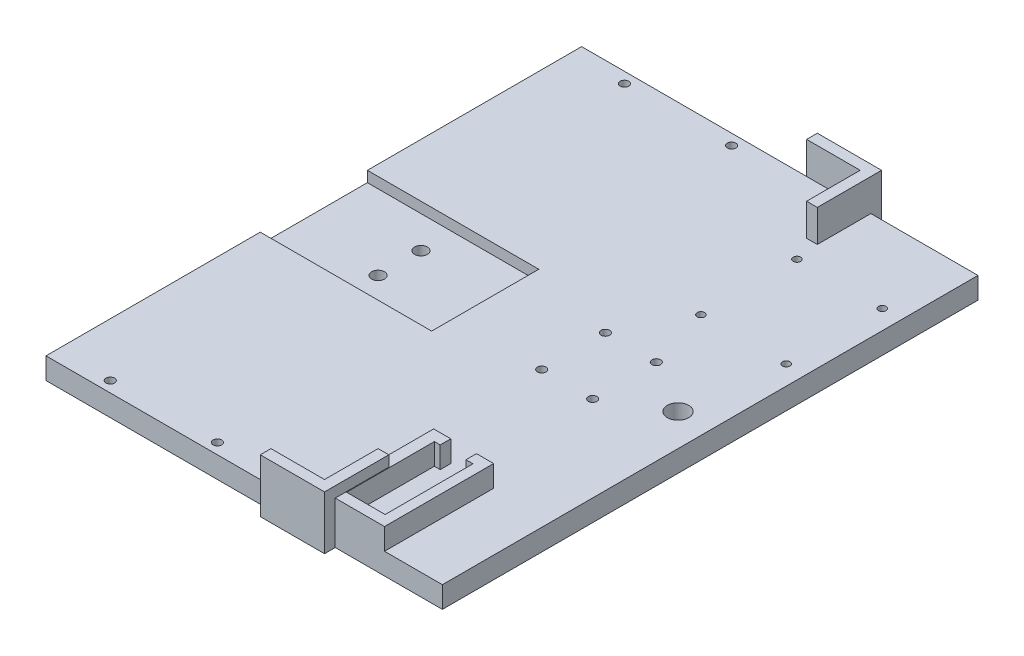
SolidWorks part; units mm, degrees
ref_plane "Ebene vorne" through (0, 0, 0) normal (0, 0, 1) x (1, 0, 0)
ref_plane "Ebene oben" through (0, 0, 0) normal (0, 1, 0) x (1, 0, 0)
ref_plane "Ebene rechts" through (0, 0, 0) normal (1, 0, 0) x (0, 0, -1)
sketch "Skizze1" plane through (0, 0, 0) normal (0, 1, 0) x (1, 0, 0)
  line L5 (-175, -125) -> (175, 125) construction
  line L6 (-175, 125) -> (175, -125) construction
  line L11 (-105, 125) -> (145, 125)
  line L12 (-105, -125) -> (-105, -65)
  line L13 (-105, 125) -> (-105, 65)
  line L14 (-105, -65) -> (-175, -65)
  line L15 (-105, 65) -> (-175, 65)
  line L17 (-105, -125) -> (145, -125)
  line L19 (185, 20) -> (145, 125)
  line L21 (175, 0) -> (175, 20)
  line L22 (175, 20) -> (185, 20)
  line L23 (185, 0) -> (185, 20)
  line L25 (185, 0) -> (185, -20)
  line L26 (185, -20) -> (175, -20)
  line L27 (175, 0) -> (175, -20)
  line L28 (185, -20) -> (145, -125)
  line L29 (-175, 65) -> (-175, -65)
  point P0 (0, 0)
  dimension "D1" = 350
  dimension "D2" = 250
  dimension "D3" = 60
  dimension "D4" = 250
  dimension "D5" = 40
  dimension "D6" = 130
  dimension "D7" = 70
  dimension "D8" = 20
  dimension "D9" = 10
extrude "Aufsatz-Linear austragen1" add sketch "Skizze1" along normal blind 15 contours L15 L29 L14 L12 L17 L28 L26 L27 L21 L22 L19 L11 L13 | L21 L27 L26 L25 L23 L22 region at (10.8182, 0, 0) region at (180, 0, 0)
sketch "Skizze2" plane through (0, 15, 0) normal (0, 1, 0) x (1, 0, 0)
  line L0 (-175, 65) -> (-175, -65) construction
  line L9 (-175, 62) -> (-110, 62)
  line L10 (-175, 62) -> (-175, 42)
  line L11 (-175, 42) -> (-110, 42)
  line L12 (-110, 62) -> (-110, 42)
  line L13 (-105, 65) -> (-175, 65) construction
  line L14 (-175, -42) -> (-110, -42)
  line L15 (-175, -42) -> (-175, -62)
  line L16 (-175, -62) -> (-110, -62)
  line L17 (-110, -42) -> (-110, -62)
  line L18 (-105, -65) -> (-175, -65) construction
  line L19 (-105, 125) -> (145, 125) construction
  line L24 (-125, -62) -> (-120, -62)
  line L25 (-125, -62) -> (-125, -65)
  line L26 (-125, -65) -> (-120, -65)
  line L27 (-120, -62) -> (-120, -65)
  line L28 (-125, -42) -> (-120, -42)
  line L29 (-125, -42) -> (-125, -38)
  line L30 (-125, -38) -> (-120, -38)
  line L31 (-120, -42) -> (-120, -38)
  line L32 (-125, 42) -> (-120, 42)
  line L33 (-125, 42) -> (-125, 38)
  line L34 (-125, 38) -> (-120, 38)
  line L35 (-120, 42) -> (-120, 38)
  line L36 (-125, 65) -> (-120, 65)
  line L37 (-125, 65) -> (-125, 62)
  line L38 (-125, 62) -> (-120, 62)
  line L39 (-120, 65) -> (-120, 62)
  line L40 (-105, -125) -> (145, -125)
  line L41 (-105, -125) -> (-105, 125)
  line L42 (-105, 125) -> (145, 125)
  line L43 (145, -125) -> (145, 125)
  line L46 (145, -125) -> (195, -125)
  line L47 (145, -125) -> (145, 125)
  line L48 (145, 125) -> (195, 125)
  line L49 (195, -125) -> (195, 125)
  line M8 (-105, 65) -> (-175, 65)
  dimension "D1" = 65
  dimension "D2" = 65
  dimension "D3" = 20
  dimension "D4" = 20
  dimension "D5" = 3
  dimension "D6" = 3
  dimension "D7" = 5
  dimension "D8" = 50
  dimension "D9" = 5
  dimension "D10" = 50
  dimension "D11" = 5
  dimension "D12" = 50
  dimension "D13" = 5
  dimension "D14" = 50
  dimension "D15" = 4
  dimension "D16" = 4
  dimension "D17" = 250
  dimension "D18" = 50
extrude "Aufsatz-Linear austragen2" add sketch "Skizze2" against normal blind 37 contours L14 L31 L30 L29 | L35 L11 L33 L34 | L39 L37 L9 M8 | L26 L27 L24 L25 region at (-122.5, 15, -63.5) region at (-122.5, 15, -40) region at (-122.5, 15, 40)
sketch "Skizze3" plane through (0, 15, 0) normal (0, 1, 0) x (1, 0, 0)
  line L0 (-105, 125) -> (145, 125) construction
  line L1 (-105, -125) -> (145, -125)
  line L2 (-105, -125) -> (-105, 125)
  line L3 (-105, 125) -> (145, 125)
  line L4 (145, -125) -> (145, 125)
  line L6 (145, -125) -> (195, -125)
  line L7 (145, -125) -> (145, 125)
  line L8 (145, 125) -> (195, 125)
  line L9 (195, -125) -> (195, 125)
  line M6 (145, -125) -> (185, -20)
  line M7 (185, -20) -> (185, 20)
  line M8 (185, 20) -> (145, 125)
  dimension "D1" = 250
  dimension "D2" = 50
extrude "Aufsatz-Linear austragen3" add sketch "Skizze3" against normal blind 15 contours L6 L9 L8 M8 M7 M6 region at (167.3825, 15, 73.4076)
sketch "Skizze4" plane through (0, 15, 0) normal (0, 1, 0) x (1, 0, 0)
  line L9 (195, -125) -> (200, -125)
  line L10 (195, -125) -> (195, 125)
  line L11 (195, 125) -> (200, 125)
  line L12 (200, -125) -> (200, 125)
  dimension "D3" = 250
  dimension "D4" = 5
extrude "Aufsatz-Linear austragen4" add sketch "Skizze4" against normal blind 15
sketch "Skizze5" plane through (0, 15, 0) normal (0, 1, 0) x (1, 0, 0)
  line L1 (-105, 125) -> (-75, 125)
  line L2 (-105, 125) -> (-105, 120)
  line L3 (-105, 120) -> (-75, 120)
  line L4 (-75, 125) -> (-75, 120)
  line L5 (-105, -125) -> (-75, -125)
  line L6 (-105, -125) -> (-105, -120)
  line L7 (-105, -120) -> (-75, -120)
  line L8 (-75, -125) -> (-75, -120)
  dimension "D1" = 30
  dimension "D2" = 30
  dimension "D3" = 5
  dimension "D4" = 5
extrude "Aufsatz-Linear austragen5" add sketch "Skizze5" against normal blind 30
sketch "Skizze6" plane through (0, 15, 0) normal (0, 1, 0) x (1, 0, 0)
  line L0 (-105, -125) -> (200, -125) construction
  line L1 (-110, -130) -> (-70.4119, -130)
  line L2 (-110, -130) -> (-110, -86.8064)
  line L3 (-110, -86.8064) -> (-70.4119, -86.8064)
  line L4 (-70.4119, -130) -> (-70.4119, -86.8064)
  line L5 (-110, 130) -> (-61.5934, 130)
  line L6 (-110, 130) -> (-110, 88.8696)
  line L7 (-110, 88.8696) -> (-61.5934, 88.8696)
  line L8 (-61.5934, 130) -> (-61.5934, 88.8696)
  line L9 (-105, -125) -> (-105, -65) construction
  line L10 (-105, 125) -> (-105, 65) construction
  line L11 (-105, 125) -> (200, 125) construction
  line L12 (-68.8744, -125) -> (-105, -125)
  line L13 (-105, -125) -> (-105, -86.8064)
  line L14 (-105, 84.0053) -> (-105, 125)
  line L15 (-105, 125) -> (-61.5934, 125)
  line M6 (-105, -65) -> (-105, -125)
  line M7 (-105, -125) -> (200, -125)
  line M9 (200, 125) -> (-105, 125)
  line M10 (-105, 125) -> (-105, 65)
  dimension "D1" = 5
  dimension "D2" = 5
  dimension "D3" = 5
  dimension "D4" = 5
extrude "Aufsatz-Linear austragen6" add sketch "Skizze6" along normal blind 15 separate body contours L8 L5 L6 L7 M10 M9 | L1 L4 L3 L2 M7 M6 region at (-109.4141, 15, 108.4032) region at (-85.7967, 15, -129.3648)
sketch "Skizze7" plane through (0, 0, 0) normal (0, -1, 0) x (1, 0, 0)
  line L7 (-110, -130) -> (-110, -88.8696)
  line L8 (-110, -88.8696) -> (-105, -88.8696)
  line L9 (-105, -130) -> (-105, -88.8696)
  line L10 (-110, 130) -> (-105, 130)
  line L11 (-110, 130) -> (-110, 86.8064)
  line L12 (-110, 86.8064) -> (-105, 86.8064)
  line L13 (-105, 130) -> (-105, 86.8064)
  line L14 (-110, 130) -> (-70.4119, 130)
  line L15 (-110, 130) -> (-110, 125)
  line L16 (-110, 125) -> (-70.4119, 125)
  line L17 (-70.4119, 130) -> (-70.4119, 125)
  line L18 (-110, -130) -> (-61.5934, -130)
  line L19 (-110, -130) -> (-110, -125)
  line L20 (-110, -125) -> (-61.5934, -125)
  line L21 (-61.5934, -130) -> (-61.5934, -125)
  line M7 (-105, 120) -> (-105, 65)
  line M19 (-105, -65) -> (-105, -120)
  line M22 (-75, -125) -> (200, -125)
  line M24 (200, 125) -> (-75, 125)
extrude "Aufsatz-Linear austragen7" add sketch "Skizze7" against normal blind 15 contours L7 L20 L9 L8 M19 | L20 L7 L18 L9 | L18 L21 L20 L9 M22 | L16 L11 L12 L13 M7 | L11 L16 L13 L10 | L17 L14 L13 L16 M24 region at (-107.5, 0, -127.5) region at (-107.5, 0, -106.9348) region at (-83.2967, 0, -127.5) region at (-107.5, 0, 127.5) region at (-87.7059, 0, 127.5) region at (-107.5, 0, 105.9032)
sketch "Skizze8" plane through (0, 15, 0) normal (0, 1, 0) x (1, 0, 0)
  line L0 (-61.5934, 125) -> (200, 125) construction
  line L1 (-105, -125) -> (145, -125)
  line L2 (-105, -125) -> (-105, 125)
  line L3 (-105, 125) -> (145, 125)
  line L4 (145, -125) -> (145, 125)
  line L6 (150, -130) -> (109.2888, -130)
  line L7 (150, -130) -> (150, -94.2536)
  line L8 (150, -94.2536) -> (109.2888, -94.2536)
  line L9 (109.2888, -130) -> (109.2888, -94.2536)
  line L10 (150, 130) -> (118.9946, 130)
  line L11 (150, 130) -> (150, 95.9912)
  line L12 (150, 95.9912) -> (118.9946, 95.9912)
  line L13 (118.9946, 130) -> (118.9946, 95.9912)
  line M9 (-70.4119, -125) -> (200, -125)
  line M11 (200, 125) -> (-61.5934, 125)
  dimension "D1" = 250
  dimension "D2" = 5
  dimension "D3" = 5
  dimension "D4" = 5
  dimension "D5" = 5
extrude "Aufsatz-Linear austragen8" add sketch "Skizze8" along normal blind 15 and the other way blind 15 contours L7 L8 L4 M9 | L9 L6 L7 L1 M9 | L12 L11 L4 M11 | L10 L13 L11 M11 region at (129.6444, 15, 127.5) region at (147.5, 15, 109.6268) region at (134.4973, 15, -127.5) region at (147.5, 15, -110.4956)
sketch "Skizze9" plane through (0, 15, 0) normal (0, 1, 0) x (1, 0, 0)
  line L1 (150, -125) -> (200, -125)
  line L2 (150, -125) -> (150, 125)
  line L3 (150, 125) -> (200, 125)
  line L4 (200, -125) -> (200, 125)
  line L5 (150, 9) -> (196, 9)
  line L6 (150, 9) -> (150, 120)
  line L7 (150, 120) -> (196, 120)
  line L8 (196, 9) -> (196, 120)
  line L10 (200, 105) -> (196, 105)
  line L12 (155, 4) -> (145, 4)
  line L13 (155, 4) -> (155, 14)
  line L14 (155, 14) -> (145, 14)
  line L15 (145, 4) -> (145, 14)
  line L17 (190, 14) -> (200, 14)
  line L18 (190, 14) -> (190, 4)
  line L19 (190, 4) -> (200, 4)
  line L20 (200, 14) -> (200, 4)
  line M10 (150, 125) -> (150, 95.9912)
  line M31 (200, 125) -> (150, 125)
  dimension "D1" = 46
  dimension "D2" = 111
  dimension "D3" = 5
  dimension "D4" = 20
  dimension "D5" = 10
  dimension "D6" = 10
  dimension "D7" = 5
  dimension "D8" = 5
  dimension "D9" = 10
  dimension "D10" = 10
  dimension "D11" = 5
extrude "Aufsatz-Linear austragen10" add sketch "Skizze9" along normal blind 15 contours L15 L12 L2 L14 | L12 L13 L5 L2 | L18 L19 L4 L17 L8 L5 | L10 L4 L7 L8 M31 M10 region at (147.5, 15, -9) region at (152.5, 15, -6.5) region at (195.8571, 15, -7.9286) region at (179.4516, 15, -120.5645)
sketch "Skizze10" plane through (118.9946, 0, 0) normal (-1, 0, 0) x (0, 0, 1)
  line L1 (-125, 30) -> (-130, 30)
  line L2 (-125, 30) -> (-125, 0)
  line L3 (-125, 0) -> (-130, 0)
  line L4 (-130, 30) -> (-130, 0)
extrude "Schnitt-Linear austragen1" cut sketch "Skizze10" against normal blind 1.01
sketch "Skizze12" plane through (0, 15, 0) normal (0, 1, 0) x (1, 0, 0)
  line L0 (-105, 125) -> (-105, 88.8696) construction
  line L1 (-110, 130) -> (-105, 130)
  line L2 (-110, 130) -> (-110, 100)
  line L3 (-110, 100) -> (-105, 100)
  line L4 (-105, 130) -> (-105, 100)
  line L5 (145, 95.9912) -> (145, 125) construction
  line L6 (-105, -125) -> (-70.4119, -125) construction
  line L7 (-110, -130) -> (-80, -130)
  line L8 (-110, -130) -> (-110, -125)
  line L9 (-110, -125) -> (-80, -125)
  line L10 (-80, -130) -> (-80, -125)
  line L11 (-61.5934, 125) -> (-105, 125) construction
  line L12 (-110, 130) -> (-80, 130)
  line L13 (-110, 130) -> (-110, 125)
  line L14 (-110, 125) -> (-80, 125)
  line L15 (-80, 130) -> (-80, 125)
  line L16 (120.0046, 125) -> (145, 125) construction
  line L17 (150, 130) -> (120, 130)
  line L18 (150, 130) -> (150, 125)
  line L19 (150, 125) -> (120, 125)
  line L20 (120, 130) -> (120, 125)
  line L21 (150, 130) -> (145, 130)
  line L22 (150, 130) -> (150, 100)
  line L23 (150, 100) -> (145, 100)
  line L24 (145, 130) -> (145, 100)
  line L25 (145, -125) -> (145, -94.2536) construction
  line L26 (150, -130) -> (145, -130)
  line L27 (150, -130) -> (150, -100)
  line L28 (150, -100) -> (145, -100)
  line L29 (145, -130) -> (145, -100)
  line L30 (109.2888, -125) -> (145, -125) construction
  line L31 (150, -130) -> (120, -130)
  line L32 (150, -130) -> (150, -125)
  line L33 (150, -125) -> (120, -125)
  line L34 (120, -130) -> (120, -125)
  line L36 (-105, -86.8064) -> (-105, -125) construction
  line L37 (-110, -130) -> (-105, -130)
  line L38 (-110, -130) -> (-110, -100)
  line L39 (-110, -100) -> (-105, -100)
  line L40 (-105, -130) -> (-105, -100)
  line L42 (-80, -125) -> (-70.4119, -125)
  line L43 (-80, -125) -> (-80, -130)
  line L44 (-80, -130) -> (-70.4119, -130)
  line L45 (-70.4119, -125) -> (-70.4119, -130)
  line L46 (-105, -100) -> (-110, -100)
  line L47 (-105, -100) -> (-105, -86.8064)
  line L48 (-105, -86.8064) -> (-110, -86.8064)
  line L49 (-110, -100) -> (-110, -86.8064)
  line L50 (-105, 100) -> (-110, 100)
  line L51 (-105, 100) -> (-105, 88.8696)
  line L52 (-105, 88.8696) -> (-110, 88.8696)
  line L53 (-110, 100) -> (-110, 88.8696)
  line L54 (-80, 125) -> (-61.5934, 125)
  line L55 (-80, 125) -> (-80, 130)
  line L56 (-80, 130) -> (-61.5934, 130)
  line L57 (-61.5934, 125) -> (-61.5934, 130)
  line L58 (150, 100) -> (145, 100)
  line L59 (150, 100) -> (150, 95.9912)
  line L60 (150, 95.9912) -> (145, 95.9912)
  line L61 (145, 100) -> (145, 95.9912)
  line L62 (150, -100) -> (145, -100)
  line L63 (150, -100) -> (150, -94.2536)
  line L64 (150, -94.2536) -> (145, -94.2536)
  line L65 (145, -100) -> (145, -94.2536)
  line L66 (120, -125) -> (109.2888, -125)
  line L67 (120, -125) -> (120, -130)
  line L68 (120, -130) -> (109.2888, -130)
  line L69 (109.2888, -125) -> (109.2888, -130)
  line M12 (150, 120) -> (150, 95.9912)
  line M13 (150, 95.9912) -> (145, 95.9912)
  line M14 (145, 95.9912) -> (145, 125)
  line M17 (-61.5934, 125) -> (-105, 125)
  line M18 (-105, 125) -> (-105, 88.8696)
  line M24 (-105, -86.8064) -> (-105, -125)
  line M25 (-105, -125) -> (-70.4119, -125)
  line M27 (109.2888, -125) -> (145, -125)
  line M28 (145, -125) -> (145, -94.2536)
  line M29 (145, -94.2536) -> (150, -94.2536)
  line M30 (150, -94.2536) -> (150, -125)
  dimension "D1" = 30
  dimension "D2" = 30
  dimension "D3" = 30
  dimension "D4" = 30
  dimension "D5" = 30
  dimension "D6" = 30
  dimension "D7" = 30
  dimension "D8" = 30
extrude "Schnitt-Linear austragen2" cut sketch "Skizze12" along normal blind 15 contours L69 L68 L34 M27 | L28 M30 M29 M28 | L23 M12 M14 M13 | L57 L56 L15 M17 | L3 L53 L52 M18 | L45 L10 L44 M25 | L49 L39 L48 M24 region at (-70.7967, 15, -127.5) region at (-107.5, 15, -94.4348) region at (-75.2059, 15, 127.5) region at (-107.5, 15, 93.4032) region at (147.5, 15, -97.9956) region at (114.6444, 15, 127.5) region at (147.5, 15, 97.1268)
sketch "Skizze13" plane through (0, 15, 0) normal (0, 1, 0) x (1, 0, 0)
  line L1 (109.2888, -130) -> (120, -130)
  line L2 (109.2888, -130) -> (109.2888, -125)
  line L3 (109.2888, -125) -> (120, -125)
  line L4 (120, -130) -> (120, -125)
  line L5 (-70.4119, -130) -> (-80, -130)
  line L6 (-70.4119, -130) -> (-70.4119, -125)
  line L7 (-70.4119, -125) -> (-80, -125)
  line L8 (-80, -130) -> (-80, -125)
  line L9 (-110, -86.8064) -> (-105, -86.8064)
  line L10 (-110, -86.8064) -> (-110, -100)
  line L11 (-110, -100) -> (-105, -100)
  line L12 (-105, -86.8064) -> (-105, -100)
  line L13 (-110, 88.8696) -> (-105, 88.8696)
  line L14 (-110, 88.8696) -> (-110, 100)
  line L15 (-110, 100) -> (-105, 100)
  line L16 (-105, 88.8696) -> (-105, 100)
  line L17 (-61.5934, 130) -> (-80, 130)
  line L18 (-61.5934, 130) -> (-61.5934, 125)
  line L19 (-61.5934, 125) -> (-80, 125)
  line L20 (-80, 130) -> (-80, 125)
extrude "Schnitt-Linear austragen3" cut sketch "Skizze13" against normal blind 15
sketch "Skizze14" plane through (0, 15, 0) normal (0, 1, 0) x (1, 0, 0)
  line L1 (-175, -65) -> (-105, -65)
  line L2 (-175, -65) -> (-175, 65)
  line L3 (-175, 65) -> (-105, 65)
  line L4 (-105, -65) -> (-105, 65)
  line L5 (-175, -25) -> (-105, -25)
  line L6 (-175, -25) -> (-175, 25)
  line L7 (-175, 25) -> (-105, 25)
  line L8 (-105, -25) -> (-105, 25)
  line L9 (-105, -25) -> (-125, -25)
  line L10 (-105, -25) -> (-105, 25)
  line L11 (-105, 25) -> (-125, 25)
  line L12 (-125, -25) -> (-125, 25)
  line M34 (-105, 65) -> (-175, 65)
  line M35 (-175, 65) -> (-175, -65)
  line M36 (-175, -65) -> (-105, -65)
  dimension "D1" = 50
  dimension "D2" = 40
  dimension "D3" = 20
  dimension "D4" = 50
extrude "Aufsatz-Linear austragen11" add sketch "Skizze14" along normal blind 20 contours L5 L2 L4 M36 | L5 L12 L7 L2 | L12 L5 L4 L7 | L7 L4 M35 M34 region at (-140, 15, 45) region at (-150, 15, 0) region at (-115, 15, 0) region at (-140, 15, -45)
chamfer "Fase2" distance 20 distance2 50 1 edges at (-175, 35, 0) first distance on face at (-175, 17.5, 0)
chamfer "Fase3" distance 20 distance2 35 2 edges at (-115, 35, -65) (-115, 35, 65) first distance on face at (-128, 5.6, -65) first distance on face at (-128, 5.6, 65)
chamfer "Fase4" distance 20 distance2 20 2 edges at (-150, 25, 47.5) (-150, 25, -47.5)
sketch "Skizze15" plane through (-11.552, 55.8863, -15.4322) normal (-0.1954, 0.9453, -0.261) x (0.9807, 0.1884, -0.052)
  line L0 (-95.2849, 28.8709) -> (-95.2849, 11.0403) construction
  line L1 (-115.678, -3.3909) -> (-166.6609, 35.67) construction
  circle A0 centre (-117.2849, 20.601) radius 10
  circle A1 centre (-142.8398, 36.3157) radius 7.5
  dimension "D1" = 20
  dimension "D2" = 15
  dimension "D3" = 30
  dimension "D4" = 22
  dimension "D5" = 15
extrude "Aufsatz-Linear austragen12" add sketch "Skizze15" along normal blind 3
fillet "Verrundung1" radius 10 2 edges at (-152.2243, 24.1474, -36.5621) (-127.1621, 33.8091, -20.3337)
sketch "Skizze18" plane through (-11.552, 55.8863, 15.4322) normal (-0.1954, 0.9453, 0.261) x (0.9807, 0.1884, 0.052)
  line L0 (-166.6609, -35.67) -> (-115.678, 3.3909) construction
  line L1 (-95.2849, -11.0403) -> (-95.2849, -28.8709) construction
  circle A0 centre (-117.2849, -25.9789) radius 10
  circle A1 centre (-147.2849, -39.7214) radius 7.5
  dimension "D1" = 20
  dimension "D2" = 15
  dimension "D3" = 30
  dimension "D4" = 15
  dimension "D5" = 22
extrude "Aufsatz-Linear austragen13" add sketch "Skizze18" along normal blind 3
fillet "Verrundung2" radius 10 2 edges at (-156.5838, 18.411, 54.0726) (-127.1621, 27.0541, 44.7961)
sketch "Skizze19" plane through (-29.3103, 73.2759, 0) normal (-0.3714, 0.9285, 0) x (0.9285, 0.3714, 0)
  line L0 (-156.9126, -41.147) -> (-156.9126, 41.147) construction
  line L1 (-103.0609, 6.147) -> (-103.0609, -6.147) construction
  line L3 (-156.9126, -41.147) -> (-103.0609, -6.147) construction
  line L4 (-103.0609, 6.147) -> (-156.9126, 41.147) construction
  circle A0 centre (-118.0609, -0.0632) radius 10
  circle A1 centre (-139.8608, 12.1747) radius 10
  circle A2 centre (-139.9126, -12.2084) radius 10
  dimension "D1" = 15
  dimension "D2" = 15
  dimension "D3" = 17
  dimension "D4" = 17.0518
  dimension "D5" = 25
  dimension "D7" = 15
  dimension "D8" = 25
extrude "Aufsatz-Linear austragen14" add sketch "Skizze19" along normal blind 3
fillet "Verrundung3" radius 10 3 edges at (-149.3261, 28.5007, 0.0632) (-169.6148, 20.3852, 12.2084) (-169.5667, 20.4044, -12.1747)
sketch "Skizze20" plane through (0, 0, -65) normal (0, 0, -1) x (-1, 0, 0)
  line L1 (120, -22) -> (125, -22) construction
  line L2 (120, 0) -> (125, 0)
  line L3 (120, -22) -> (120, 0) construction
  line L4 (125, -22) -> (125, 0) construction
  circle A0 centre (122.5, -19.5) radius 1.5
  circle A1 centre (122.5, -2.5) radius 1.5
  dimension "D1" = 3
  dimension "D2" = 3
  dimension "D3" = 2.5
  dimension "D4" = 2.5
  dimension "D5" = 2.5
  dimension "D6" = 2.5
extrude "Schnitt-Linear austragen4" cut sketch "Skizze20" against normal blind 250 contours A0 | A1 region at (-122.5, -19.5, -65) region at (-122.5, -2.5, -65)
sketch "Skizze21" plane through (0, 15, 0) normal (0, 1, 0) x (1, 0, 0)
  line L0 (200, -125) -> (200, 4) construction
  line L1 (197.5893, -53.9558) -> (147.5893, -53.9558)
  line L2 (197.5893, -53.9558) -> (197.5893, 1.0442)
  line L3 (197.5893, 1.0442) -> (147.5893, 1.0442)
  line L4 (147.5893, -53.9558) -> (147.5893, 1.0442)
  line L9 (150, -100) -> (191, -100)
  line L10 (150, -100) -> (150, -118)
  line L11 (150, -118) -> (191, -118)
  line L12 (191, -100) -> (191, -118)
  line L13 (145, -100) -> (195, -100)
  line L14 (145, -100) -> (145, -93)
  line L15 (145, -93) -> (195, -93)
  line L16 (195, -100) -> (195, -93)
  line L17 (150, -125) -> (200, -125)
  line L18 (150, -125) -> (150, -118)
  line L19 (150, -118) -> (200, -118)
  line L20 (200, -125) -> (200, -118)
  line L22 (195, -93) -> (191, -93)
  line L23 (195, -93) -> (195, -105.2)
  line L24 (195, -105.2) -> (191, -105.2)
  line L25 (191, -93) -> (191, -105.2)
  line L26 (195, -125) -> (191, -125)
  line L27 (195, -125) -> (195, -112.8)
  line L28 (195, -112.8) -> (191, -112.8)
  line L29 (191, -125) -> (191, -112.8)
  line M31 (145, -100) -> (150, -100)
  line M32 (150, -100) -> (150, -125)
  line M33 (150, -125) -> (200, -125)
  dimension "D1" = 55
  dimension "D2" = 50
  dimension "D3" = 41
  dimension "D4" = 18
  dimension "D5" = 7
  dimension "D6" = 4
  dimension "D7" = 12.2
  dimension "D8" = 4
  dimension "D9" = 12.2
extrude "Aufsatz-Linear austragen15" add sketch "Skizze21" along normal blind 10 contours L25 L15 L14 L9 M31 | L15 L25 L13 L16 | L24 L23 L13 L12 | L29 L11 M33 M32 | L29 L17 L27 L19 | L27 L28 L12 L19 region at (168, 15, 96.5) region at (193, 15, 102.6) region at (193, 15, 96.5) region at (170.5, 15, 121.5) region at (193, 15, 115.4) region at (193, 15, 121.5)
sketch "Skizze22" plane through (0, 15, 0) normal (0, 1, 0) x (1, 0, 0)
  line L1 (140.9695, -63.333) -> (190.9695, -63.333)
  line L2 (140.9695, -63.333) -> (140.9695, -8.333)
  line L3 (140.9695, -8.333) -> (190.9695, -8.333)
  line L4 (190.9695, -63.333) -> (190.9695, -8.333)
  circle A0 centre (146.0695, -58.233) radius 1.75
  circle A1 centre (146.0695, -13.433) radius 1.75
  circle A2 centre (185.8695, -58.233) radius 1.75
  circle A3 centre (185.8695, -13.433) radius 1.75
  dimension "D1" = 3.5
  dimension "D2" = 3.5
  dimension "D3" = 3.5
  dimension "D4" = 3.5
  dimension "D5" = 5.1
  dimension "D6" = 5.1
  dimension "D7" = 50
  dimension "D8" = 55
  dimension "D9" = 5.1
  dimension "D10" = 5.1
  dimension "D11" = 5.1
  dimension "D12" = 5.1
  dimension "D13" = 5.1
  dimension "D14" = 5.1
extrude "Schnitt-Linear austragen5" cut sketch "Skizze22" against normal blind 20 contours A0 | A1 | A3 | A2
sketch "Skizze23" plane through (0, 15, 0) normal (0, 1, 0) x (1, 0, 0)
  line L0 (200, 14) -> (200, 105) construction
  line L1 (-175, 149.5923) -> (15, 149.5923)
  line L2 (-175, 149.5923) -> (-175, -153.0489)
  line L3 (-175, -153.0489) -> (15, -153.0489)
  line L4 (15, 149.5923) -> (15, -153.0489)
  dimension "D1" = 190
  dimension "D2" = 185
extrude "Schnitt-Linear austragen6" cut sketch "Skizze23" against normal blind 47 and the other way blind 59 contours L2 L1 L4 L3
sketch "Skizze24" plane through (15, 0, 0) normal (-1, 0, 0) x (0, 0, 1)
  line L0 (125, 15) -> (-125, 15) construction
  line L1 (-25, 15) -> (25, 15)
  line L2 (-25, 15) -> (-25, 10)
  line L3 (-25, 10) -> (25, 10)
  line L4 (25, 15) -> (25, 10)
  line L5 (-125, 0) -> (-125, 15) construction
  dimension "D1" = 50
  dimension "D2" = 5
  dimension "D3" = 100
extrude "Schnitt-Linear austragen7" cut sketch "Skizze24" against normal blind 80
sketch "Skizze25" plane through (0, 10, 0) normal (0, 1, 0) x (1, 0, 0)
  line L0 (95, -25) -> (95, 25) construction
  line L1 (95, -25) -> (15, -25) construction
  circle A0 centre (65, 0) radius 12.5
  dimension "D1" = 25
  dimension "D2" = 30
  dimension "D3" = 25
extrude "Schnitt-Linear austragen8" cut sketch "Skizze25" against normal blind 80
sketch "Skizze26" plane through (0, 0, 0) normal (0, -1, 0) x (1, 0, 0)
  circle A0 centre (65, 0) radius 17.5909
extrude "Aufsatz-Linear austragen16" add sketch "Skizze26" against normal blind 10
sketch "Skizze27" plane through (0, 15, 0) normal (0, 1, 0) x (1, 0, 0)
  line L5 (95, 25) -> (15, 25)
  line L6 (95, 25) -> (95, -25)
  line L7 (95, -25) -> (15, -25)
  line L8 (15, 25) -> (15, -25)
  circle A0 centre (75, 10) radius 3
  circle A1 centre (75, -10) radius 3
  circle A2 centre (35, 10) radius 3
  circle A3 centre (35, -10) radius 3
  dimension "D7" = 6
  dimension "D8" = 6
  dimension "D11" = 6
  dimension "D12" = 6
  dimension "D1" = 40
  dimension "D2" = 20
  dimension "D3" = 20
  dimension "D4" = 40
  dimension "D5" = 20
  dimension "D6" = 15
  dimension "D9" = 20
  dimension "D10" = 15
extrude "Schnitt-Linear austragen10" cut sketch "Skizze27" against normal blind 93 contours A0 | A1 | A2 | A3
sketch "Skizze28" plane through (0, 15, 0) normal (0, 1, 0) x (1, 0, 0)
  line L0 (95, 25) -> (95, 0)
  line L5 (95, -25) -> (95, 25) construction
  line L6 (95, 0) -> (200, 0)
  line L7 (200, -125) -> (200, 4) construction
  line L8 (200, 14) -> (200, 105) construction
  circle A0 centre (160, -14.85) radius 2
  circle A1 centre (160, 14.85) radius 2
  circle A2 centre (136.2, 14.85) radius 2
  circle A3 centre (136.2, -14.85) radius 2
  dimension "D3" = 4
  dimension "D4" = 4
  dimension "D5" = 4
  dimension "D6" = 4
  dimension "D1" = 29.7
  dimension "D2" = 29.7
  dimension "D7" = 23.8
  dimension "D8" = 23.8
  dimension "D9" = 14.85
  dimension "D10" = 14.85
  dimension "D11" = 40
  dimension "D12" = 40
extrude "Schnitt-Linear austragen11" cut sketch "Skizze28" against normal blind 93 contours A1 | A0 | A3 | A2 region at (160, 15, 14.85) region at (160, 15, -14.85) region at (136.2, 15, -14.85) region at (136.2, 15, 14.85)
sketch "Skizze29" plane through (0, 15, 0) normal (0, 1, 0) x (1, 0, 0)
  line L1 (145, 125) -> (15, 125)
  line L2 (15, 25) -> (15, 125) construction
  line L3 (15, -125) -> (15, -25) construction
  line L4 (15, -125) -> (120, -125) construction
  circle A0 centre (90, 120) radius 2
  circle A1 centre (40, 120) radius 2
  circle A2 centre (90, -120) radius 2
  circle A3 centre (40, -120) radius 2
  dimension "D1" = 4
  dimension "D2" = 4
  dimension "D3" = 4
  dimension "D4" = 4
  dimension "D5" = 50
  dimension "D6" = 25
  dimension "D7" = 5
  dimension "D8" = 5
  dimension "D9" = 50
  dimension "D10" = 25
  dimension "D11" = 5
extrude "Schnitt-Linear austragen13" cut sketch "Skizze29" against normal blind 20 contours A0 | A1 | A2 | A3 region at (90, 15, -120) region at (40, 15, -120) region at (90, 15, 120) region at (40, 15, 120)
sketch "Skizze30" plane through (0, 10, 0) normal (0, 1, 0) x (1, 0, 0)
  line L1 (95, 25) -> (15, 25)
  line L2 (95, 25) -> (95, -25)
  line L3 (95, -25) -> (15, -25)
  line L4 (15, 25) -> (15, -25)
extrude "Aufsatz-Linear austragen17" add sketch "Skizze30" against normal blind 7
sketch "Skizze31" plane through (0, 10, 0) normal (0, 1, 0) x (1, 0, 0)
  line L0 (95, 25) -> (15, 25) construction
  line L1 (95, -25) -> (95, 25) construction
  circle A0 centre (55, 10) radius 3
  circle A1 centre (55, -10) radius 3
  dimension "D1" = 6
  dimension "D2" = 6
  dimension "D3" = 20
  dimension "D4" = 15
  dimension "D5" = 40
extrude "Schnitt-Linear austragen14" cut sketch "Skizze31" against normal blind 27
sketch "Skizze32" plane through (0, 0, 0) normal (0, -1, 0) x (1, 0, 0)
  circle A0 centre (75, -10) radius 3
  circle A1 centre (75, 10) radius 3.7236
  circle A2 centre (35, 10) radius 5.2534
  circle A3 centre (35, -10) radius 5.5871
extrude "Aufsatz-Linear austragen18" add sketch "Skizze32" against normal blind 9
sketch "Skizze35" plane through (0, 15, 0) normal (0, 1, 0) x (1, 0, 0)
  line L1 (197.0348, -115.503) -> (233.2763, -115.503)
  line L2 (197.0348, -115.503) -> (197.0348, -91.503)
  line L3 (197.0348, -91.503) -> (233.2763, -91.503)
  line L4 (233.2763, -115.503) -> (233.2763, -91.503)
  circle A0 centre (146.0695, -58.233) radius 1.75
  circle A1 centre (146.0695, -13.433) radius 1.75
  circle A2 centre (185.8695, -13.433) radius 1.75
  circle A3 centre (185.8695, -58.233) radius 1.75
  circle A4 centre (151.2105, 44.4776) radius 1.75
  circle A5 centre (191.0105, 44.4785) radius 1.75
  circle A6 centre (151.2105, 89.2776) radius 1.75
  circle A7 centre (191.0105, 89.2785) radius 1.75
  dimension "D4" = 3.5
  dimension "D5" = 3.5
  dimension "D6" = 3.5
  dimension "D7" = 3.5
  dimension "D1" = 24
  dimension "D2" = 44.8
  dimension "D3" = 39.8
  dimension "D8" = 39.8
  dimension "D9" = 44.8
  dimension "D10" = 39.8
  dimension "D11" = 44.8
extrude "Schnitt-Linear austragen16" cut sketch "Skizze35" against normal blind 20 contours A4 | A6 | A5 | A7
sketch "Skizze36" plane through (0, 15, 0) normal (0, 1, 0) x (1, 0, 0)
  circle A0 centre (146.0971, -61.909) radius 6.8466
  circle A1 centre (186.6852, -57.9261) radius 4.4713
  circle A2 centre (186.6852, -12.786) radius 4.8942
  circle A3 centre (146.0971, -12.786) radius 3.5251
extrude "Aufsatz-Linear austragen19" add sketch "Skizze36" against normal blind 15
sketch "Skizze39" plane through (0, 15, 0) normal (0, 1, 0) x (1, 0, 0)
  line L1 (200, -125) -> (150, -125)
  line L2 (200, -125) -> (200, 125)
  line L3 (200, 125) -> (150, 125)
  line L4 (150, -125) -> (150, 125)
extrude "Schnitt-Linear austragen17" cut sketch "Skizze39" along normal blind 57
sketch "Skizze40" plane through (0, 15, 0) normal (0, 1, 0) x (1, 0, 0)
  line L1 (154.2583, 18.1172) -> (142.8019, 18.1172)
  line L2 (154.2583, 18.1172) -> (154.2583, -99.7777)
  line L3 (154.2583, -99.7777) -> (142.8019, -99.7777)
  line L4 (142.8019, 18.1172) -> (142.8019, -99.7777)
extrude "Schnitt-Linear austragen18" cut sketch "Skizze40" along normal blind 86
sketch "Skizze41" plane through (0, 15, 0) normal (0, 1, 0) x (1, 0, 0)
  line L1 (150.3591, -99.2895) -> (145, -99.2895)
  line L2 (150.3591, -99.2895) -> (150.3591, -100)
  line L3 (150.3591, -100) -> (145, -100)
  line L4 (145, -99.2895) -> (145, -100)
extrude "Schnitt-Linear austragen19" cut sketch "Skizze41" along normal blind 69
sketch "Skizze42" plane through (0, 15, 0) normal (0, 1, 0) x (1, 0, 0)
  line L1 (150.2826, -120) -> (168.2826, -120)
  line L2 (150.2826, -120) -> (150.2826, -79)
  line L3 (150.2826, -79) -> (168.2826, -79)
  line L4 (168.2826, -120) -> (168.2826, -79)
  line L5 (145, -125) -> (173, -125)
  line L6 (145, -125) -> (145, -74.0666)
  line L7 (145, -74.0666) -> (173, -74.0666)
  line L8 (173, -125) -> (173, -74.0666)
  line L9 (153, -74.0666) -> (165, -74.0666)
  line L10 (153, -74.0666) -> (153, -79)
  line L11 (153, -79) -> (165, -79)
  line L12 (165, -74.0666) -> (165, -79)
  line M14 (145, -100) -> (150, -100)
  line M15 (150, -100) -> (150, -125)
  line M16 (150, -125) -> (200, -125)
  dimension "D1" = 18
  dimension "D2" = 41
  dimension "D3" = 12
  dimension "D4" = 8
  dimension "D5" = 8
  dimension "D6" = 5
extrude "Aufsatz-Linear austragen20" add sketch "Skizze42" along normal blind 10 contours L7 L12 L3 L4 L1 L2 L10 L6 L8 M14 M15 M16 region at (159.2826, 15, 120.5812)
sketch "Skizze44" plane through (0, 0, -125) normal (0, 0, -1) x (-1, 0, 0)
  line L0 (-15, 15) -> (-15, 0) construction
  line L1 (-200, 0) -> (-15, 0)
  line L2 (-200, 0) -> (-200, 5)
  line L3 (-200, 5) -> (-15, 5)
  line L4 (-15, 0) -> (-15, 5)
  dimension "D1" = 5
extrude "Schnitt-Linear austragen20" cut sketch "Skizze44" against normal blind 345 and the other way blind 48
sketch "Skizze45" plane through (0, 15, 0) normal (0, 1, 0) x (1, 0, 0)
  line L0 (200, -125) -> (200, 125) construction
  circle A0 centre (185, 0) radius 5
  point P2 (182.8994, 0)
  dimension "D1" = 10
  dimension "D2" = 15
extrude "Schnitt-Linear austragen21" cut sketch "Skizze45" against normal blind 10
